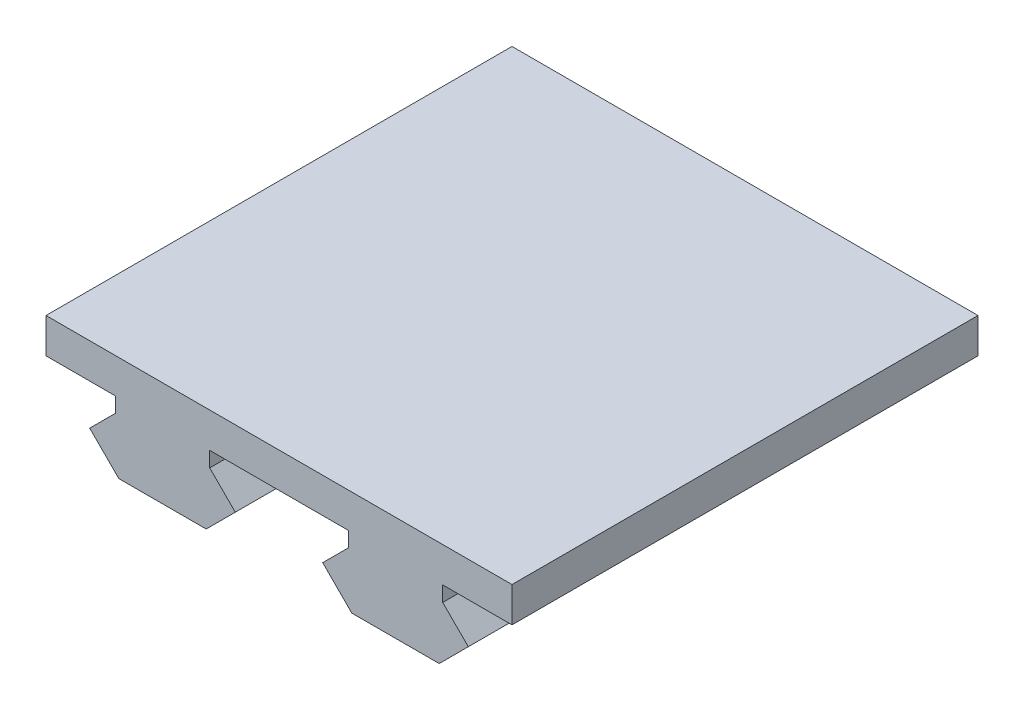
SolidWorks part; units mm, degrees
ref_plane "Front Plane" through (0, 0, 0) normal (0, 0, 1) x (1, 0, 0)
ref_plane "Top Plane" through (0, 0, 0) normal (0, 1, 0) x (1, 0, 0)
ref_plane "Right Plane" through (0, 0, 0) normal (1, 0, 0) x (0, 0, -1)
sketch "Sketch1" plane through (0, 0, 0) normal (0, 1, 0) x (1, 0, 0)
  line L1 (-20, -20) -> (20, -20)
  line L2 (-20, -20) -> (-20, 20)
  line L3 (-20, 20) -> (20, 20)
  line L4 (20, -20) -> (20, 20)
  line L5 (-20, -20) -> (20, 20) construction
  line L6 (-20, 20) -> (20, -20) construction
  point P0 (0, 0)
  dimension "D1" = 40
  dimension "D2" = 40
extrude "Boss-Extrude1" add sketch "Sketch1" along normal blind 3
sketch "Sketch2" plane through (0, 0, 20) normal (0, 0, 1) x (1, 0, 0)
  line L0 (0, 0) -> (-20, 0) construction
  line L1 (-20, 0) -> (20, 0) construction
  line L2 (-10, 0) -> (-10, -6) construction
  line L3 (-13.75, -6) -> (-6.25, -6)
  line L4 (-13.75, -6) -> (-16.25, -3.5)
  line L5 (-16.25, -3.5) -> (-14.0535, -1.3035)
  line L6 (-14.0535, -1.3035) -> (-14.0535, 0)
  line L7 (-14.0535, 0) -> (-5.9465, 0)
  line L8 (-5.9465, -1.3035) -> (-5.9465, 0)
  line L9 (-3.75, -3.5) -> (-5.9465, -1.3035)
  line L10 (-6.25, -6) -> (-3.75, -3.5)
  point P10 (-10, -6)
  dimension "D1" = 7.5
  dimension "D2" = 12.5
  dimension "D3" = 135
  dimension "D4" = 6
  dimension "D5" = 90
  dimension "D6" = 6
extrude "Boss-Extrude2" add sketch "Sketch2" against normal up to surface (40 mm away) up to face at (0, 1.5, -20)
sketch "Sketch3" plane through (0, 0, 0) normal (1, 0, 0) x (0, 0, -1)
  line L0 (20, -6) -> (-20, -6) construction
  line L1 (20, 0) -> (-20, 0) construction
  line L2 (20, -6) -> (-20, -6)
  line L3 (20, 0) -> (-20, 0)
  line L4 (0, -6) -> (0, 0) construction
  line L6 (-6.6667, -6) -> (6.6667, -6)
  line L7 (-6.6667, -6) -> (-6.6667, 0)
  line L8 (-6.6667, 0) -> (6.6667, 0)
  line L9 (6.6667, -6) -> (6.6667, 0)
  line L10 (-6.6667, -6) -> (6.6667, 0) construction
  line L11 (-6.6667, 0) -> (6.6667, -6) construction
  point P7 (0, -3)
  dimension "D1" = 40
  dimension "D2" = 13.3333
extrude "Cut-Extrude1" cut sketch "Sketch3" against normal through all contours L2 L9 L3 L7 region at (0, -3, 0)
mirror "Mirror1" about plane through (0, 0, 0) normal (1, 0, 0) of "Boss-Extrude2", "Cut-Extrude1"
